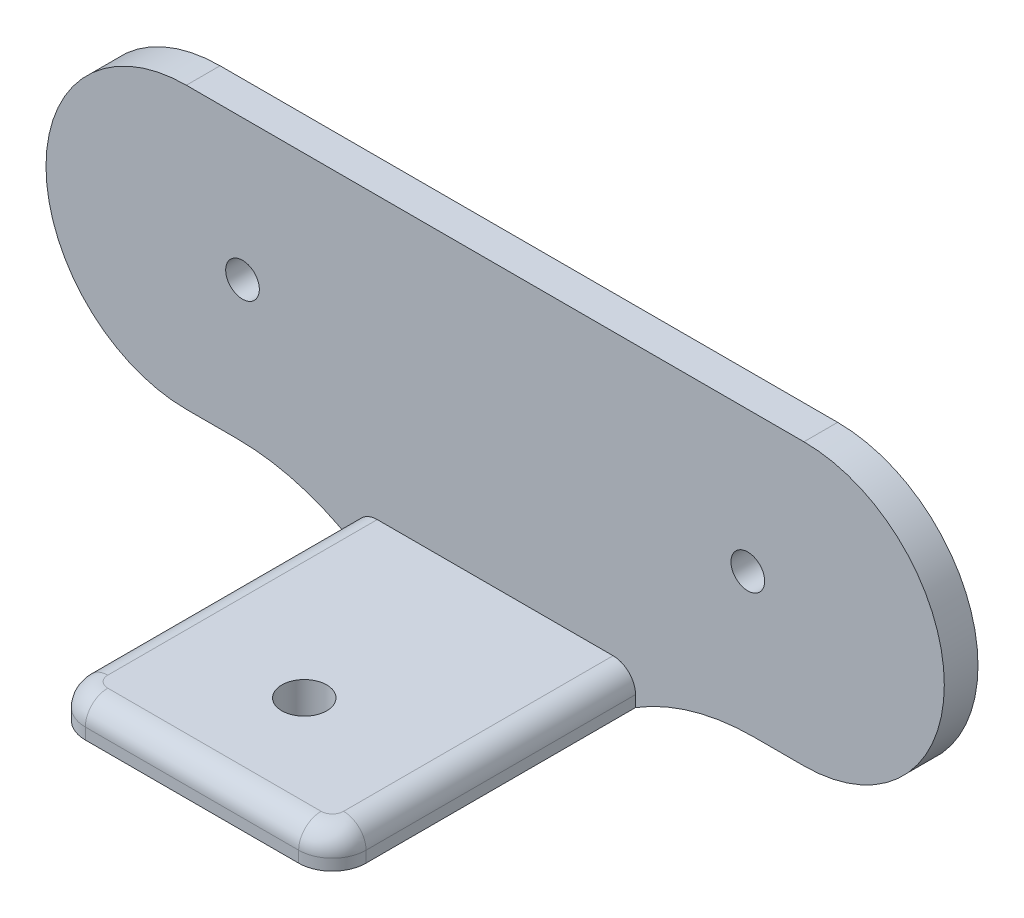
SolidWorks part; units mm, degrees
ref_plane "Plan de face" through (0, 0, 0) normal (0, 0, 1) x (1, 0, 0)
ref_plane "Plan de dessus" through (0, 0, 0) normal (0, 1, 0) x (1, 0, 0)
ref_plane "Plan de droite" through (0, 0, 0) normal (1, 0, 0) x (0, 0, -1)
sketch "Esquisse1" plane through (0, 0, 0) normal (0, 0, 1) x (1, 0, 0)
  line L0 (-27.5, 0) -> (27.5, 0)
  line L1 (27.5, -25) -> (-27.5, -25)
  arc A0 (27.5, 0) -> (27.5, -25) centre (27.5, -12.5) cw
  arc A1 (-27.5, -25) -> (-27.5, 0) centre (-27.5, -12.5) cw
  dimension "D1" = 55
  dimension "D2" = 25
extrude "Boss.-Extru.1" add sketch "Esquisse1" along normal blind 3
sketch "Esquisse2" plane through (0, 0, 3) normal (0, 0, 1) x (1, 0, 0)
  line L0 (-22.5, -12.5) -> (22.5, -12.5) construction
  circle A0 centre (-22.5, -12.5) radius 1.5
  circle A1 centre (22.5, -12.5) radius 1.5
  arc A2 (-27.5, 0) -> (-27.5, -25) centre (-27.5, -12.5) ccw construction
  point P4 (0, -12.5)
  point P5 (-22.5, -6.8749)
  point P10 (-40, -12.5)
  dimension "D2" = 3
  dimension "D3" = 3
  dimension "D1" = 45
extrude "Enlèv. mat.-Extru.1" cut sketch "Esquisse2" against normal through all
sketch "Esquisse3" plane through (0, -25, 0) normal (0, -1, 0) x (1, 0, 0)
  line L0 (-27.5, 0) -> (27.5, 0) construction
  line L1 (-12.5, 0) -> (12.5, 0)
  line L2 (-12.5, 0) -> (-12.5, 27)
  line L3 (-9.5, 30) -> (9.5, 30)
  line L4 (12.5, 0) -> (12.5, 27)
  arc A0 (9.5, 30) -> (12.5, 27) centre (9.5, 27) cw
  arc A1 (-12.5, 27) -> (-9.5, 30) centre (-9.5, 27) cw
  point P9 (12.5, 30)
  point P12 (-12.5, 30)
  dimension "D3" = 3
  dimension "D1" = 30
  dimension "D2" = 25
extrude "Boss.-Extru.2" add sketch "Esquisse3" along normal blind 3
fillet "Congé1" radius 20 2 edges at (12.5, -25, 1.5) (-12.5, -25, 1.5)
sketch "Esquisse4" plane through (0, -25, 0) normal (0, 1, 0) x (1, 0, 0)
  line L0 (9.5, -30) -> (-9.5, -30) construction
  circle A0 centre (0, -20) radius 2
  point P4 (0, 0)
  point P5 (0, -30)
  dimension "D2" = 4
  dimension "D1" = 10
extrude "Enlèv. mat.-Extru.2" cut sketch "Esquisse4" against normal through all
fillet "Congé3" radius 2 5 edges at (12.5, -25, 15) (11.6213, -25, 29.1213) (0, -25, 30) (-11.6213, -25, 29.1213) (-12.5, -25, 15)
